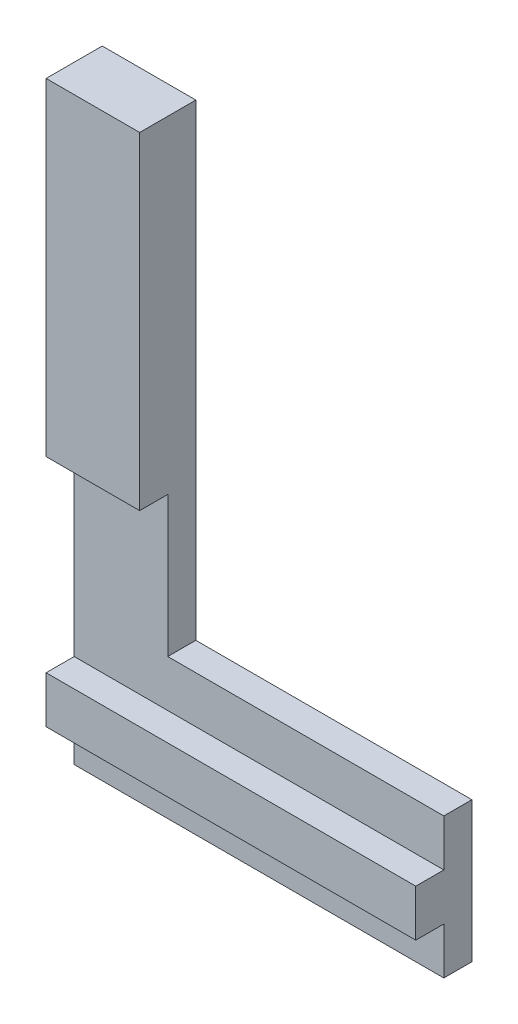
SolidWorks part; units mm, degrees
ref_plane "Front Plane" through (0, 0, 0) normal (0, 0, 1) x (1, 0, 0)
ref_plane "Top Plane" through (0, 0, 0) normal (0, 1, 0) x (1, 0, 0)
ref_plane "Right Plane" through (0, 0, 0) normal (1, 0, 0) x (0, 0, -1)
sketch "Sketch1" plane through (0, 0, 0) normal (0, 0, 1) x (1, 0, 0)
  line L0 (0, 0) -> (0, 100)
  line L1 (0, 100) -> (20, 100)
  line L3 (79, 0) -> (0, 0)
  line L4 (0, 0) -> (0, -30)
  line L5 (0, -30) -> (79, -30)
  line L6 (79, -30) -> (79, 0)
  line L7 (20, 100) -> (20, 0)
  line L9 (0, 0) -> (20, 0)
  line L26 (0, 0) -> (0, -30)
  dimension "D1" = 100
  dimension "D2" = 20
  dimension "D3" = 79
  dimension "D4" = 30
extrude "Boss-Extrude4" add sketch "Sketch1" along normal blind 6 contours L7 L1 L0 L3 region at (10, 50, 0)
extrude "Boss-Extrude5" add sketch "Sketch1<8>" along normal blind 6 contours L5 L6 L3 L4 region at (39.5, -15, 0)
sketch "Sketch1<8>" plane through (0, 0, 0) normal (0, 0, 1) x (1, 0, 0) same geometry as "Sketch1"
sketch "Sketch3" plane through (0, 0, 6) normal (0, 0, 1) x (1, 0, 0)
  line L0 (0, -30) -> (0, 100) construction
  line L1 (0, -10) -> (79, -10)
  line L2 (0, -10) -> (0, -20)
  line L3 (0, -20) -> (79, -20)
  line L4 (79, -10) -> (79, -20)
  line L5 (79, -30) -> (79, 0) construction
  dimension "D1" = 10
  dimension "D2" = 10
extrude "Boss-Extrude6" add sketch "Sketch3" along normal blind 6
sketch "Sketch6" plane through (0, 0, 6) normal (0, 0, 1) x (1, 0, 0)
  line L0 (0, 30) -> (20, 30)
  line L1 (0, 100) -> (20, 100)
  line L2 (0, 100) -> (0, 0)
  line L4 (20, 100) -> (20, 0)
  line M4 (20, 0) -> (20, 100)
  line M5 (20, 100) -> (0, 100)
  line M6 (0, 100) -> (0, -10)
  dimension "D1" = 70
extrude "Boss-Extrude8" add sketch "Sketch6" along normal blind 6 contours L0 M6 M4 M5 region at (10, 65, 6)
